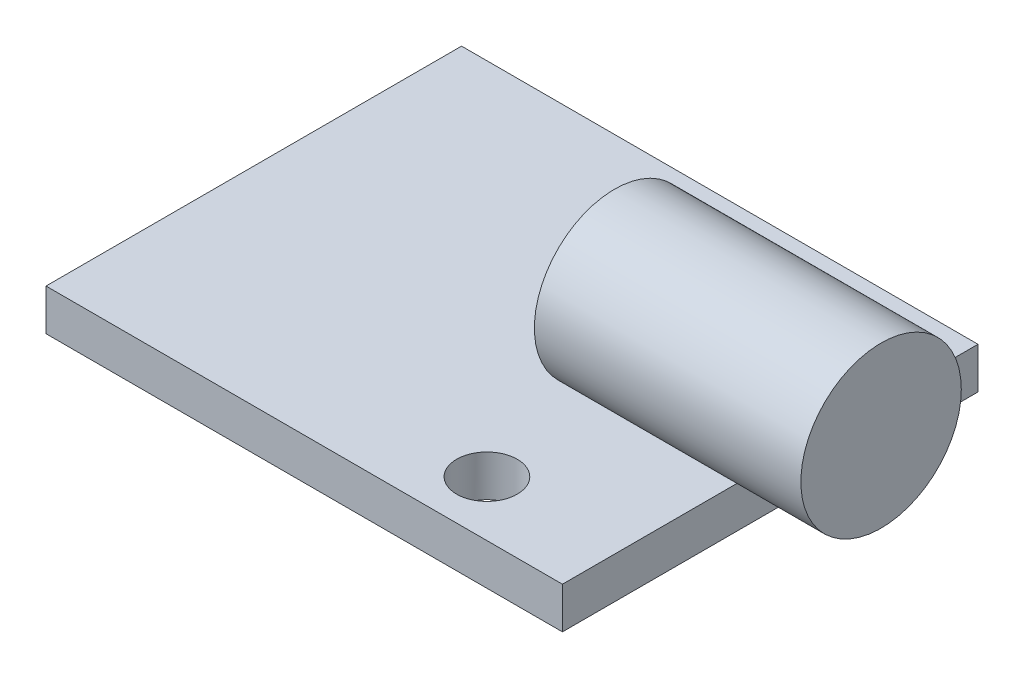
SolidWorks part; units mm, degrees
ref_plane "Front Plane" through (0, 0, 0) normal (0, 0, 1) x (1, 0, 0)
ref_plane "Top Plane" through (0, 0, 0) normal (0, 1, 0) x (1, 0, 0)
ref_plane "Right Plane" through (0, 0, 0) normal (1, 0, 0) x (0, 0, -1)
sketch "Sketch1" plane through (0, 0, 0) normal (0, 1, 0) x (1, 0, 0)
  line L1 (0, 0) -> (19.05, 0)
  line L2 (0, 0) -> (0, -15.3289)
  line L3 (0, -15.3289) -> (19.05, -15.3289)
  line L4 (19.05, 0) -> (19.05, -15.3289)
  dimension "D1" = 19.05
  dimension "D2" = 15.3289
extrude "Boss-Extrude1" add sketch "Sketch1" along normal blind 1.524 contours L2 L1 L4 L3
sketch "Sketch3" plane through (19.05, 0, 0) normal (1, 0, 0) x (0, 0, -1)
  circle A0 centre (-7.6645, 4.4831) radius 2.9591
  dimension "D1" = 5.9182
extrude "Boss-Extrude2" add sketch "Sketch3" along normal blind 4.0894 and the other way blind 5.7404 separate body
sketch "Sketch6" plane through (0, 1.524, 0) normal (0, 1, 0) x (1, 0, 0)
  line L0 (19.05, 0) -> (19.05, -15.3289) construction
  circle A0 centre (14.224, -13.2872) radius 1.1176
  circle A1 centre (14.224, -2.7843) radius 1.1176
  dimension "D1" = 2.2352
  dimension "D4" = 2.2352
  dimension "D2" = 4.826
  dimension "D5" = 10.5029
extrude "Cut-Extrude1" cut sketch "Sketch6" against normal blind 4.0894
